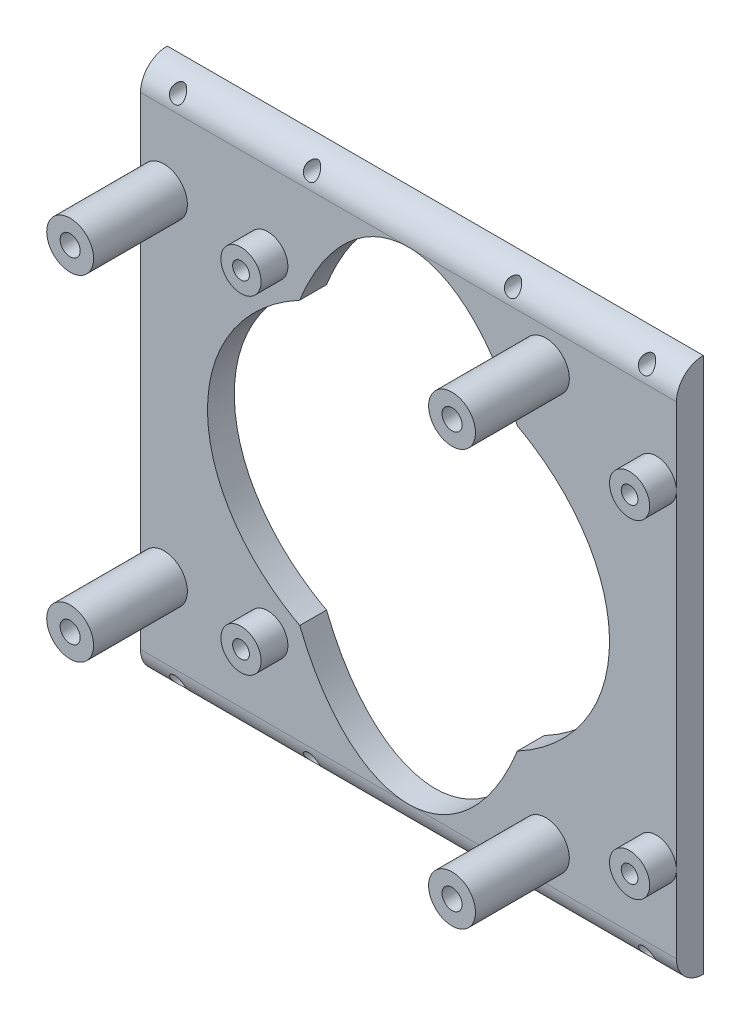
SolidWorks part; units mm, degrees
ref_plane "Alzado" through (0, 0, 0) normal (0, 0, 1) x (1, 0, 0)
ref_plane "Planta" through (0, 0, 0) normal (0, 1, 0) x (1, 0, 0)
ref_plane "Vista lateral" through (0, 0, 0) normal (1, 0, 0) x (0, 0, -1)
sketch "Croquis1" plane through (0, 0, 0) normal (0, 0, 1) x (1, 0, 0)
  line L0 (-50.9465, -21.9298) -> (-50.9465, -17.9298) construction
  line L1 (-50.9465, 58.0702) -> (29.0535, 58.0702)
  line L2 (-50.9465, 58.0702) -> (-50.9465, -21.9298)
  line L3 (-50.9465, -21.9298) -> (29.0535, -21.9298)
  line L4 (29.0535, 58.0702) -> (29.0535, -21.9298)
  line L5 (-50.9465, 58.0702) -> (-50.9465, 54.0702) construction
  line L6 (29.0535, -21.9298) -> (19.0535, -21.9298) construction
  line L7 (-50.9465, -17.9298) -> (29.0535, -17.9298)
  line L8 (-50.9465, -17.9298) -> (-50.9465, -21.9298)
  line L9 (-50.9465, -21.9298) -> (29.0535, -21.9298)
  line L10 (29.0535, -17.9298) -> (29.0535, -21.9298)
  line L11 (-50.9465, 54.0702) -> (29.0535, 54.0702)
  line L12 (-50.9465, 54.0702) -> (-50.9465, 58.0702)
  line L13 (-50.9465, 58.0702) -> (29.0535, 58.0702)
  line L14 (29.0535, 54.0702) -> (29.0535, 58.0702)
  line L15 (-50.9465, -21.9298) -> (-40.9465, -21.9298) construction
  line L16 (-50.9465, 18.0702) -> (29.0535, 18.0702) construction
  line L17 (29.0535, -21.9298) -> (19.0535, -21.9298)
  line L18 (29.0535, -21.9298) -> (29.0535, 58.0702)
  line L19 (29.0535, 58.0702) -> (19.0535, 58.0702)
  line L20 (19.0535, -21.9298) -> (19.0535, 58.0702)
  line L21 (-50.9465, 58.0702) -> (-40.9465, 58.0702)
  line L22 (-50.9465, 58.0702) -> (-50.9465, -21.9298)
  line L23 (-50.9465, -21.9298) -> (-40.9465, -21.9298)
  line L24 (-40.9465, 58.0702) -> (-40.9465, -21.9298)
  line L29 (19.0535, -21.9298) -> (9.5535, -21.9298) construction
  line L30 (29.0535, 18.0702) -> (29.0535, -6.4298) construction
  line L31 (29.0535, 18.0702) -> (29.0535, 42.5702) construction
  line L32 (29.0535, 42.5702) -> (-50.9465, 42.5702) construction
  line L33 (29.0535, -6.4298) -> (-50.9465, -6.4298) construction
  line L34 (29.0535, -6.4298) -> (26.0535, -6.4298) construction
  line L35 (-50.9465, 18.0702) -> (-50.9465, 43.0702) construction
  line L36 (-50.9465, 18.0702) -> (-50.9465, -6.9298) construction
  line L37 (-50.9465, 18.0702) -> (-50.9465, 49.0702) construction
  line L38 (-50.9465, 18.0702) -> (-50.9465, -12.9298) construction
  line L39 (-50.9465, 49.0702) -> (29.0535, 49.0702) construction
  line L40 (-50.9465, -12.9298) -> (29.0535, -12.9298) construction
  line L41 (9.5535, -21.9298) -> (9.5535, 58.0702) construction
  line L42 (9.5535, -12.9298) -> (-47.4465, -12.9298) construction
  line L43 (-47.4465, -21.9298) -> (-47.4465, 58.0702) construction
  line L44 (26.0535, -21.9298) -> (26.0535, 58.0702) construction
  line L45 (-50.9465, 43.0702) -> (29.0535, 43.0702) construction
  line L46 (-50.9465, -6.9298) -> (29.0535, -6.9298) construction
  line L47 (26.0535, -6.4298) -> (-31.9465, -6.4298) construction
  line L48 (-40.9465, 58.0702) -> (-40.9465, 68.0702) construction
  line L49 (-40.9465, -21.9298) -> (-40.9465, -31.9298) construction
  line L50 (-50.9465, -21.9298) -> (-40.9465, -31.9298) construction
  line L51 (-50.9465, -21.9298) -> (-40.9465, -21.9298)
  line L52 (-50.9465, -21.9298) -> (-50.9465, -31.9298)
  line L53 (-50.9465, -31.9298) -> (-40.9465, -31.9298)
  line L54 (-40.9465, -21.9298) -> (-40.9465, -31.9298)
  line L55 (19.0535, -21.9298) -> (29.0535, -21.9298)
  line L56 (19.0535, -21.9298) -> (19.0535, -31.9298)
  line L57 (19.0535, -31.9298) -> (29.0535, -31.9298)
  line L58 (29.0535, -21.9298) -> (29.0535, -31.9298)
  line L59 (-50.9465, 58.0702) -> (-40.9465, 58.0702)
  line L60 (-50.9465, 58.0702) -> (-50.9465, 68.0702)
  line L61 (-50.9465, 68.0702) -> (-40.9465, 68.0702)
  line L62 (-40.9465, 58.0702) -> (-40.9465, 68.0702)
  line L63 (19.0535, 58.0702) -> (29.0535, 58.0702)
  line L64 (19.0535, 58.0702) -> (19.0535, 68.0702)
  line L65 (19.0535, 68.0702) -> (29.0535, 68.0702)
  line L66 (29.0535, 58.0702) -> (29.0535, 68.0702)
  line L67 (-50.9465, -31.9298) -> (-40.9465, -21.9298) construction
  line L68 (19.0535, -21.9298) -> (29.0535, -31.9298) construction
  line L69 (19.0535, -31.9298) -> (29.0535, -21.9298) construction
  line L70 (19.0535, 68.0702) -> (29.0535, 58.0702) construction
  line L71 (29.0535, 68.0702) -> (19.0535, 58.0702) construction
  line L72 (-50.9465, 58.0702) -> (-40.9465, 68.0702) construction
  line L73 (-40.9465, 58.0702) -> (-50.9465, 68.0702) construction
  line L74 (-10.9465, 58.0702) -> (-10.9465, -21.9298)
  line L75 (-30.9465, 58.0702) -> (-30.9465, -21.9298)
  line L76 (9.0535, 58.0702) -> (9.0535, -21.9298)
  line L77 (-20.9465, 58.0702) -> (-20.9465, -21.9298)
  line L78 (-0.9465, 58.0702) -> (-0.9465, -21.9298)
  line L79 (-50.9465, 13.0702) -> (29.0535, 13.0702)
  line L80 (-50.9465, 23.0702) -> (29.0535, 23.0702)
  line L82 (-50.9465, 13.0702) -> (29.0535, 13.0702)
  line L83 (-50.9465, 13.0702) -> (-50.9465, 23.0702)
  line L84 (-50.9465, 23.0702) -> (29.0535, 23.0702)
  line L85 (29.0535, 13.0702) -> (29.0535, 23.0702)
  line L86 (-50.9465, -21.9298) -> (29.0535, -21.9298)
  line L87 (-50.9465, -21.9298) -> (-50.9465, -17.9298)
  line L88 (-50.9465, -17.9298) -> (29.0535, -17.9298)
  line L89 (29.0535, -21.9298) -> (29.0535, -17.9298)
  line L90 (-50.9465, 54.0702) -> (29.0535, 54.0702)
  line L91 (-50.9465, 54.0702) -> (-50.9465, 58.0702)
  line L92 (-50.9465, 58.0702) -> (29.0535, 58.0702)
  line L93 (29.0535, 54.0702) -> (29.0535, 58.0702)
  circle A0 centre (9.5535, -12.9298) radius 3.5
  circle A1 centre (9.5535, 49.0702) radius 3.5
  circle A2 centre (9.5535, 49.0702) radius 1.5
  circle A3 centre (9.5535, -12.9298) radius 1.5
  circle A4 centre (9.5535, 49.0702) radius 2.2
  circle A5 centre (9.5535, -12.9298) radius 2.2
  circle A12 centre (26.0535, 42.5702) radius 3
  circle A13 centre (26.0535, -6.4298) radius 3
  circle A14 centre (-47.4465, 43.0702) radius 3.5
  circle A15 centre (-47.4465, 43.0702) radius 2.2
  circle A16 centre (-47.4465, 43.0702) radius 1.5
  circle A17 centre (-47.4465, -6.9298) radius 3.5
  circle A18 centre (-47.4465, -6.9298) radius 2.2
  circle A19 centre (-47.4465, -6.9298) radius 1.5
  circle A20 centre (26.0535, -6.4298) radius 1.25
  circle A21 centre (26.0535, 42.5702) radius 1.25
  circle A22 centre (-31.9465, -6.4298) radius 3
  circle A23 centre (-31.9465, -6.4298) radius 1.25
  circle A24 centre (-31.9465, 42.5702) radius 3
  circle A25 centre (-31.9465, 42.5702) radius 1.25
  circle A26 centre (-45.9465, 63.0702) radius 1.5
  circle A27 centre (24.0535, 63.0702) radius 1.5
  circle A28 centre (24.0535, -26.9298) radius 1.5
  circle A29 centre (-45.9465, -26.9298) radius 1.5
  dimension "D15" = 57
  dimension "D16" = 58
  dimension "D19" = 20
  dimension "D1" = 80
  dimension "D2" = 80
  dimension "D3" = 4
  dimension "D4" = 4
  dimension "D5" = 10
  dimension "D6" = 10
  dimension "D7" = 9.5
  dimension "D8" = 24.5
  dimension "D9" = 24.5
  dimension "D10" = 3
  dimension "D11" = 25
  dimension "D12" = 25
  dimension "D13" = 31
  dimension "D14" = 31
  dimension "D20" = 20
  dimension "D21" = 10
  dimension "D22" = 10
  dimension "D23" = 5
  dimension "D24" = 5
extrude "Saliente-Extruir5" add sketch "Croquis1" along normal blind 4 contours L1 L62 L61 L60 A26 | L13 L66 L65 L64 A27 | L58 L9 L56 L57 A28 | L54 L3 L52 L53 A29 | L24 L7 L2 L3 | L75 L7 L24 L9 | L77 L7 L75 L3 | L7 L77 L9 L74 | L78 L7 L74 L3 | L7 L78 L9 L76 | L7 L76 L9 L20 | L20 L9 L4 L7 | A13 A20 | A20 | L4 A13 L18 L79 L20 L7 | L22 A17 L2 L7 L24 L79 | A17 A18 | A18 A19 | A19 | L80 L22 L79 L24 | L80 L24 L79 L75 | L80 L75 L79 L77 | L80 L77 L79 L74 | L80 L74 L79 L78 | L80 L78 L79 L76 | L80 L76 L79 L20 | L80 L20 L79 L18 | L2 A14 L22 L80 L24 L11 | L24 L1 L2 L11 | A14 A15 | A15 A16 | A16 | L75 L13 L24 L11 | L77 L1 L75 L11 | L13 L77 L11 L74 | L78 L1 L74 L11 | L13 L78 L11 L76 | L13 L76 L11 L20 | L20 L11 L4 L13 | L18 A12 L4 L11 L20 L80 | A12 A21 | A21 region at (-50.8051, 63.0702, 0) region at (-45.9465, 56.0702, 0) region at (-35.9465, 56.0702, 0) region at (-47.4465, 46.4712, 0) region at (-45.7339, 37.9323, 0) region at (-25.9465, 56.0702, 0) region at (-15.9465, 56.0702, 0) region at (-35.9465, 18.0702, 0) region at (-45.9465, 18.0702, 0) region at (-5.9465, 56.0702, 0) region at (-47.4465, -3.5288, 0) region at (-45.7339, -1.792, 0) region at (-25.9465, 18.0702, 0) region at (4.0535, 56.0702, 0) region at (-15.9465, 18.0702, 0) region at (-45.9465, -19.9298, 0) region at (-35.9465, -19.9298, 0) region at (14.0535, 56.0702, 0) region at (-5.9465, 18.0702, 0) region at (-25.9465, -19.9298, 0) region at (-41.0879, -26.9298, 0) region at (19.1949, 63.0702, 0) region at (24.0535, 56.0702, 0) region at (4.0535, 18.0702, 0) region at (-15.9465, -19.9298, 0) region at (23.1383, 42.5702, 0) region at (23.8528, 38.1687, 0) region at (14.0535, 18.0702, 0) region at (-5.9465, -19.9298, 0) region at (24.0535, 18.0702, 0) region at (4.0535, -19.9298, 0) region at (23.1383, -6.4298, 0) region at (23.8528, -2.0284, 0) region at (14.0535, -19.9298, 0) region at (24.0535, -19.9298, 0) region at (24.0535, -22.0712, 0) region at (-49.5843, 43.0702, 0) region at (-47.4465, 43.0702, 0) region at (-49.5843, -6.9298, 0) region at (-47.4465, -6.9298, 0) region at (26.0535, -6.4298, 0) region at (26.0535, 42.5702, 0)
extrude "Saliente-Extruir6" add sketch "Croquis1<6>" along normal blind 20.4 from surface contours L24 L1 L2 L11 | L77 L1 L75 L11 | L20 L11 L4 L13 | L13 L78 L11 L76 | L24 L7 L2 L3 | L77 L7 L75 L3 | L7 L78 L9 L76 | L20 L9 L4 L7 region at (-45.9465, 56.0702, 0) region at (-25.9465, 56.0702, 0) region at (4.0535, 56.0702, 0) region at (-45.9465, -19.9298, 0) region at (-25.9465, -19.9298, 0) region at (24.0535, 56.0702, 0) region at (4.0535, -19.9298, 0) region at (24.0535, -19.9298, 0) starting at face at (-10.9465, -2.4298, 4)
sketch "Croquis1<6>" plane through (0, 0, 0) normal (0, 0, 1) x (1, 0, 0) same geometry as "Croquis1"
extrude "Saliente-Extruir7" add sketch "Croquis1<7>" along normal blind 4 from surface contours L24 L1 L2 L11 | L75 L13 L24 L11 | L13 L77 L11 L74 | L78 L1 L74 L11 | L13 L78 L11 L76 | L77 L1 L75 L11 | L13 L76 L11 L20 | L18 A12 L4 L11 L20 L80 | L2 A14 L22 L80 L24 L11 | A24 L75 L11 L24 L80 | A14 A15 | A15 A16 | A16 | A12 A21 | A21 | L20 L11 L4 L13 | A25 L75 A24 | L75 A25 | A25 L75 A24 | L75 A25 | A24 L75 L80 L77 L11 | L77 L80 L74 L11 | L74 L80 L78 L11 | A1 L76 L11 L78 L80 | A4 L76 A1 | L76 A4 A2 | L76 A2 | L76 A2 | L76 A4 A2 | A4 L76 A1 | A1 L76 L80 L20 L11 | L80 L20 L79 L18 | L80 L76 L79 L20 | L80 L78 L79 L76 | L80 L74 L79 L78 | L80 L77 L79 L74 | L80 L75 L79 L77 | L80 L24 L79 L75 | L80 L22 L79 L24 | A22 L75 L79 L24 L7 | A22 L75 L7 L77 L79 | L79 L77 L7 L74 | L79 L74 L7 L78 | A0 L76 L79 L78 L7 | A0 L76 L7 L20 L79 | L22 A17 L2 L7 L24 L79 | A17 A18 | A18 A19 | A19 | A23 L75 A22 | L75 A23 | L75 A23 | A23 L75 A22 | A13 A20 | A20 | L76 A3 | L76 A3 | L76 A5 A3 | A5 L76 A0 | L76 A5 A3 | A5 L76 A0 | L20 L9 L4 L7 | L7 L76 L9 L20 | L7 L78 L9 L76 | L78 L7 L74 L3 | L7 L77 L9 L74 | L77 L7 L75 L3 | L75 L7 L24 L9 | L24 L7 L2 L3 | L4 A13 L18 L79 L20 L7 region at (-45.9465, 56.0702, 0) region at (-35.9465, 56.0702, 0) region at (-47.4465, 46.4712, 0) region at (-45.7339, 37.9323, 0) region at (-25.9465, 56.0702, 0) region at (-36.1707, 38.294, 0) region at (-15.9465, 56.0702, 0) region at (-25.8325, 38.4608, 0) region at (-35.9465, 18.0702, 0) region at (-45.9465, 18.0702, 0) region at (-5.9465, 56.0702, 0) region at (-15.9465, 38.5702, 0) region at (-30.0948, 42.5702, 0) region at (-31.0186, 44.3594, 0) region at (-36.1707, -2.1536, 0) region at (-47.4465, -3.5288, 0) region at (-45.7339, -1.792, 0) region at (-25.9465, 18.0702, 0) region at (4.0535, 56.0702, 0) region at (-5.9465, 38.5702, 0) region at (-15.9465, 18.0702, 0) region at (-30.8456, 42.5702, 0) region at (-32.007, 42.5702, 0) region at (-45.9465, -19.9298, 0) region at (-35.9465, -19.9298, 0) region at (-25.8325, -2.3205, 0) region at (14.0535, 56.0702, 0) region at (3.8532, 38.008, 0) region at (-5.9465, 18.0702, 0) region at (-15.9465, -2.4298, 0) region at (-25.9465, -19.9298, 0) region at (-30.0948, -6.4298, 0) region at (-31.0186, -4.6406, 0) region at (24.0535, 56.0702, 0) region at (14.3131, 37.7394, 0) region at (4.0535, 18.0702, 0) region at (-5.9465, -2.4298, 0) region at (-15.9465, -19.9298, 0) region at (-30.8456, -6.4298, 0) region at (-32.007, -6.4298, 0) region at (23.1383, 42.5702, 0) region at (23.8528, 38.1687, 0) region at (11.792, 51.655, 0) region at (8.978, 51.8734, 0) region at (3.8532, -1.8676, 0) region at (14.0535, 18.0702, 0) region at (-5.9465, -19.9298, 0) region at (24.0535, 18.0702, 0) region at (10.8889, 50.7531, 0) region at (9.0074, 50.8485, 0) region at (4.0535, -19.9298, 0) region at (14.3131, -1.599, 0) region at (23.1383, -6.4298, 0) region at (23.8528, -2.0284, 0) region at (9.9301, 49.0702, 0) region at (8.6393, 49.0702, 0) region at (14.0535, -19.9298, 0) region at (11.792, -10.345, 0) region at (8.978, -10.1266, 0) region at (24.0535, -19.9298, 0)
sketch "Croquis1<7>" plane through (0, 0, 0) normal (0, 0, 1) x (1, 0, 0) same geometry as "Croquis1"
extrude "Saliente-Extruir9" add sketch "Croquis1<10>" along normal blind 4 from surface contours A24 | A12 | A13 | A22 starting at face at (-10.9465, 18.0702, 28.4)
sketch "Croquis1<10>" plane through (0, 0, 0) normal (0, 0, 1) x (1, 0, 0) same geometry as "Croquis1"
extrude "Saliente-Extruir10" add sketch "Croquis1<11>" along normal blind 14 from surface contours A14 | A17 | A0 | A1 starting at face at (-34.9465, -6.4298, 28.4)
sketch "Croquis1<11>" plane through (0, 0, 0) normal (0, 0, 1) x (1, 0, 0) same geometry as "Croquis1"
extrude "Cortar-Extruir1" cut sketch "Croquis1<12>" against normal blind 14 and the other way blind 14 from surface contours A19 | A23 | A3 | A20 | A21 | A2 | A25 | A16 starting at face at (6.0535, 49.0702, 28.4)
sketch "Croquis1<12>" plane through (0, 0, 0) normal (0, 0, 1) x (1, 0, 0) same geometry as "Croquis1"
extrude "Cortar-Extruir2" cut sketch "Croquis1<13>" along normal blind 15 from surface contours A5 | A18 | A15 | A4 starting at face at (-33.1965, -6.4298, 24.4)
sketch "Croquis1<13>" plane through (0, 0, 0) normal (0, 0, 1) x (1, 0, 0) same geometry as "Croquis1"
fillet "Redondeo2" 2 edges at (-40.9465, 68.0702, 2) (-50.9465, 68.0702, 2) type full round first side face at (-40.9465, 63.0702, 2) second side face at (-50.9465, 18.0702, 12.96) middle face at (-45.9465, 68.0702, 2)
fillet "Redondeo3" 2 edges at (-50.9465, -31.9298, 2) (-40.9465, -31.9298, 2) type full round first side face at (-50.9465, 17.0702, 12.96) second side face at (-40.9465, -26.9298, 2) middle face at (-45.9465, -31.9298, 2)
fillet "Redondeo4" 2 edges at (19.0535, -31.9298, 2) (29.0535, -31.9298, 2) type full round first side face at (19.0535, -26.9298, 2) second side face at (29.0535, 18.0702, 12.96) middle face at (24.0535, -31.9298, 2)
fillet "Redondeo5" 2 edges at (19.0535, 68.0702, 2) (29.0535, 68.0702, 2) type full round first side face at (19.0535, 63.0702, 2) second side face at (29.0535, 19.0702, 12.96) middle face at (24.0535, 68.0702, 2)
sketch "Croquis2" plane through (0, 0, 0) normal (0, 0, 1) x (1, 0, 0)
  line L0 (-50.9465, -21.9298) -> (-50.9465, -17.9298) construction
  line L1 (-50.9465, 58.0702) -> (29.0535, 58.0702)
  line L2 (-50.9465, 58.0702) -> (-50.9465, -21.9298)
  line L3 (-50.9465, -21.9298) -> (29.0535, -21.9298)
  line L4 (29.0535, 58.0702) -> (29.0535, -21.9298)
  line L5 (-50.9465, 58.0702) -> (-50.9465, 54.0702) construction
  line L6 (29.0535, -21.9298) -> (19.0535, -21.9298) construction
  line L7 (-50.9465, -17.9298) -> (29.0535, -17.9298)
  line L8 (-50.9465, -17.9298) -> (-50.9465, -21.9298)
  line L9 (-50.9465, -21.9298) -> (29.0535, -21.9298)
  line L10 (29.0535, -17.9298) -> (29.0535, -21.9298)
  line L11 (-50.9465, 54.0702) -> (29.0535, 54.0702)
  line L12 (-50.9465, 54.0702) -> (-50.9465, 58.0702)
  line L13 (-50.9465, 58.0702) -> (29.0535, 58.0702)
  line L14 (29.0535, 54.0702) -> (29.0535, 58.0702)
  line L15 (-50.9465, -21.9298) -> (-40.9465, -21.9298) construction
  line L16 (-50.9465, 18.0702) -> (29.0535, 18.0702) construction
  line L17 (29.0535, -21.9298) -> (19.0535, -21.9298)
  line L18 (29.0535, -21.9298) -> (29.0535, 58.0702)
  line L19 (29.0535, 58.0702) -> (19.0535, 58.0702)
  line L20 (19.0535, -21.9298) -> (19.0535, 58.0702)
  line L21 (-50.9465, 58.0702) -> (-40.9465, 58.0702)
  line L22 (-50.9465, 58.0702) -> (-50.9465, -21.9298)
  line L23 (-50.9465, -21.9298) -> (-40.9465, -21.9298)
  line L24 (-40.9465, 58.0702) -> (-40.9465, -21.9298)
  line L29 (19.0535, -21.9298) -> (9.5535, -21.9298) construction
  line L30 (29.0535, 18.0702) -> (29.0535, -6.4298) construction
  line L31 (29.0535, 18.0702) -> (29.0535, 42.5702) construction
  line L32 (29.0535, 42.5702) -> (-50.9465, 42.5702) construction
  line L33 (29.0535, -6.4298) -> (-50.9465, -6.4298) construction
  line L34 (29.0535, -6.4298) -> (26.0535, -6.4298) construction
  line L35 (-50.9465, 18.0702) -> (-50.9465, 43.0702) construction
  line L36 (-50.9465, 18.0702) -> (-50.9465, -6.9298) construction
  line L37 (-50.9465, 18.0702) -> (-50.9465, 49.0702) construction
  line L38 (-50.9465, 18.0702) -> (-50.9465, -12.9298) construction
  line L39 (-50.9465, 49.0702) -> (29.0535, 49.0702) construction
  line L40 (-50.9465, -12.9298) -> (29.0535, -12.9298) construction
  line L41 (9.5535, -21.9298) -> (9.5535, 58.0702) construction
  line L42 (9.5535, -12.9298) -> (-47.4465, -12.9298) construction
  line L43 (-47.4465, -21.9298) -> (-47.4465, 58.0702) construction
  line L44 (26.0535, -21.9298) -> (26.0535, 58.0702) construction
  line L45 (-50.9465, 43.0702) -> (29.0535, 43.0702) construction
  line L46 (-50.9465, -6.9298) -> (29.0535, -6.9298) construction
  line L47 (26.0535, -6.4298) -> (-31.9465, -6.4298) construction
  line L48 (-40.9465, 58.0702) -> (-40.9465, 68.0702) construction
  line L49 (-40.9465, -21.9298) -> (-40.9465, -31.9298) construction
  line L50 (-50.9465, -21.9298) -> (-40.9465, -31.9298) construction
  line L51 (-50.9465, -21.9298) -> (-40.9465, -21.9298)
  line L52 (-50.9465, -21.9298) -> (-50.9465, -31.9298)
  line L53 (-50.9465, -31.9298) -> (-40.9465, -31.9298)
  line L54 (-40.9465, -21.9298) -> (-40.9465, -31.9298)
  line L55 (19.0535, -21.9298) -> (29.0535, -21.9298)
  line L56 (19.0535, -21.9298) -> (19.0535, -31.9298)
  line L57 (19.0535, -31.9298) -> (29.0535, -31.9298)
  line L58 (29.0535, -21.9298) -> (29.0535, -31.9298)
  line L59 (-50.9465, 58.0702) -> (-40.9465, 58.0702)
  line L60 (-50.9465, 58.0702) -> (-50.9465, 68.0702)
  line L61 (-50.9465, 68.0702) -> (-40.9465, 68.0702)
  line L62 (-40.9465, 58.0702) -> (-40.9465, 68.0702)
  line L63 (19.0535, 58.0702) -> (29.0535, 58.0702)
  line L64 (19.0535, 58.0702) -> (19.0535, 68.0702)
  line L65 (19.0535, 68.0702) -> (29.0535, 68.0702)
  line L66 (29.0535, 58.0702) -> (29.0535, 68.0702)
  line L67 (-50.9465, -31.9298) -> (-40.9465, -21.9298) construction
  line L68 (19.0535, -21.9298) -> (29.0535, -31.9298) construction
  line L69 (19.0535, -31.9298) -> (29.0535, -21.9298) construction
  line L70 (19.0535, 68.0702) -> (29.0535, 58.0702) construction
  line L71 (29.0535, 68.0702) -> (19.0535, 58.0702) construction
  line L72 (-50.9465, 58.0702) -> (-40.9465, 68.0702) construction
  line L73 (-40.9465, 58.0702) -> (-50.9465, 68.0702) construction
  line L74 (-10.9465, 58.0702) -> (-10.9465, -21.9298)
  line L75 (-30.9465, 58.0702) -> (-30.9465, -21.9298)
  line L76 (9.0535, 58.0702) -> (9.0535, -21.9298)
  line L77 (-20.9465, 58.0702) -> (-20.9465, -21.9298)
  line L78 (-0.9465, 58.0702) -> (-0.9465, -21.9298)
  line L79 (-50.9465, 13.0702) -> (29.0535, 13.0702)
  line L80 (-50.9465, 23.0702) -> (29.0535, 23.0702)
  line L82 (-50.9465, 13.0702) -> (29.0535, 13.0702)
  line L83 (-50.9465, 13.0702) -> (-50.9465, 23.0702)
  line L84 (-50.9465, 23.0702) -> (29.0535, 23.0702)
  line L85 (29.0535, 13.0702) -> (29.0535, 23.0702)
  line L86 (-50.9465, -21.9298) -> (29.0535, -21.9298)
  line L87 (-50.9465, -21.9298) -> (-50.9465, -17.9298)
  line L88 (-50.9465, -17.9298) -> (29.0535, -17.9298)
  line L89 (29.0535, -21.9298) -> (29.0535, -17.9298)
  line L90 (-50.9465, 54.0702) -> (29.0535, 54.0702)
  line L91 (-50.9465, 54.0702) -> (-50.9465, 58.0702)
  line L92 (-50.9465, 58.0702) -> (29.0535, 58.0702)
  line L93 (29.0535, 54.0702) -> (29.0535, 58.0702)
  circle A0 centre (9.5535, -12.9298) radius 3.5
  circle A1 centre (9.5535, 49.0702) radius 3.5
  circle A2 centre (9.5535, 49.0702) radius 1.5
  circle A3 centre (9.5535, -12.9298) radius 1.5
  circle A4 centre (9.5535, 49.0702) radius 2.2
  circle A5 centre (9.5535, -12.9298) radius 2.2
  circle A12 centre (26.0535, 42.5702) radius 3
  circle A13 centre (26.0535, -6.4298) radius 3
  circle A14 centre (-47.4465, 43.0702) radius 3.5
  circle A15 centre (-47.4465, 43.0702) radius 2.2
  circle A16 centre (-47.4465, 43.0702) radius 1.5
  circle A17 centre (-47.4465, -6.9298) radius 3.5
  circle A18 centre (-47.4465, -6.9298) radius 2.2
  circle A19 centre (-47.4465, -6.9298) radius 1.5
  circle A20 centre (26.0535, -6.4298) radius 1.25
  circle A21 centre (26.0535, 42.5702) radius 1.25
  circle A22 centre (-31.9465, -6.4298) radius 3
  circle A23 centre (-31.9465, -6.4298) radius 1.25
  circle A24 centre (-31.9465, 42.5702) radius 3
  circle A25 centre (-31.9465, 42.5702) radius 1.25
  circle A26 centre (-45.9465, 63.0702) radius 1.5
  circle A27 centre (24.0535, 63.0702) radius 1.5
  circle A28 centre (24.0535, -26.9298) radius 1.5
  circle A29 centre (-45.9465, -26.9298) radius 1.5
  ellipse E0 centre (-10.9465, 18.0702) end of major axis (-40.9465, 18.0702) minor radius 25
  ellipse E1 centre (-10.9465, 18.0702) end of major axis (-10.9465, -17.9298) minor radius 20
  dimension "D15" = 57
  dimension "D16" = 58
  dimension "D19" = 20
  dimension "D1" = 80
  dimension "D2" = 80
  dimension "D3" = 4
  dimension "D4" = 4
  dimension "D5" = 10
  dimension "D6" = 10
  dimension "D7" = 9.5
  dimension "D8" = 24.5
  dimension "D9" = 24.5
  dimension "D10" = 3
  dimension "D11" = 25
  dimension "D12" = 25
  dimension "D13" = 31
  dimension "D14" = 31
  dimension "D20" = 20
  dimension "D21" = 10
  dimension "D22" = 10
  dimension "D23" = 5
  dimension "D24" = 5
fillet "Redondeo6" radius 4 1 edges at (-10.9465, -21.9298, 28.4) type face fillet first side face at (-10.9465, -21.9298, 11.65) second side face at (6.0535, 49.0702, 28.4)
fillet "Redondeo7" radius 4 1 edges at (-10.9465, 58.0702, 28.4) type face fillet first side face at (-10.9465, 58.0702, 11.65) second side face at (6.0535, 49.0702, 28.4)
extrude "Cortar-Extruir6" cut sketch "Croquis2" against normal blind 8 from surface contours E1 | E0 starting at face at (6.0535, 49.0702, 28.4)
sketch "Croquis3" plane through (0, -21.9298, 0) normal (0, -1, 0) x (1, 0, 0)
  line L0 (-40.9465, 24.4) -> (-50.9465, 24.4) construction
  line L1 (-50.9465, 24.4) -> (29.0535, 24.4)
  line L2 (-50.9465, 24.4) -> (-50.9465, 0)
  line L3 (-50.9465, 0) -> (29.0535, 0)
  line L4 (29.0535, 24.4) -> (29.0535, 0)
extrude "Cortar-Extruir7" cut sketch "Croquis3" against normal blind 90 and the other way blind 10
sketch "Croquis4" plane through (0, 0, 24.4) normal (0, 0, -1) x (-1, 0, 0)
  line L0 (50.9465, 58.0702) -> (50.9465, 54.0702) construction
  line L1 (50.9465, 54.0702) -> (-29.0535, 54.0702) construction
  line L2 (-29.0535, -21.9298) -> (-29.0535, 58.0702) construction
  line L3 (-29.0535, 54.0702) -> (-29.0535, 58.0702) construction
  line L4 (-29.0535, 58.0702) -> (50.9465, 58.0702) construction
  line L5 (-29.0535, 58.0702) -> (-19.0535, 58.0702) construction
  line L6 (50.9465, 58.0702) -> (-29.0535, 58.0702)
  line L7 (50.9465, 58.0702) -> (50.9465, 54.0702)
  line L8 (50.9465, 54.0702) -> (-29.0535, 54.0702)
  line L9 (-29.0535, 58.0702) -> (-29.0535, 54.0702)
  line L10 (-19.0535, 58.0702) -> (-9.0535, 58.0702) construction
  line L11 (-9.0535, 58.0702) -> (0.9465, 58.0702) construction
  line L12 (50.9465, 58.0702) -> (40.9465, 58.0702) construction
  line L13 (40.9465, 58.0702) -> (30.9465, 58.0702) construction
  line L14 (30.9465, 58.0702) -> (20.9465, 58.0702) construction
  line L15 (-19.0535, 58.0702) -> (-19.0535, -21.9298) construction
  line L16 (50.9465, -21.9298) -> (-29.0535, -21.9298)
  line L17 (50.9465, -21.9298) -> (50.9465, -17.9298)
  line L18 (50.9465, -17.9298) -> (-29.0535, -17.9298)
  line L19 (-29.0535, -21.9298) -> (-29.0535, -17.9298)
  line L20 (-19.0535, -21.9298) -> (-9.0535, -21.9298) construction
  line L21 (-9.0535, -21.9298) -> (-9.0535, 58.0702) construction
  line L22 (-9.0535, 58.0702) -> (0.9465, 58.0702) construction
  line L23 (0.9465, 58.0702) -> (0.9465, -21.9298) construction
  line L24 (0.9465, -21.9298) -> (20.9465, 58.0702) construction
  line L25 (20.9465, 58.0702) -> (20.9465, -21.9298) construction
  line L26 (20.9465, -21.9298) -> (30.9465, -21.9298) construction
  line L27 (30.9465, -21.9298) -> (30.9465, 58.0702) construction
  line L28 (30.9465, 58.0702) -> (40.9465, 58.0702) construction
  line L29 (40.9465, 58.0702) -> (40.9465, -21.9298) construction
  line L30 (50.9465, 56.0702) -> (-29.0535, 56.0702)
  line L31 (50.9465, 58.0702) -> (40.9465, 58.0702)
  line L32 (50.9465, 58.0702) -> (50.9465, 54.0702)
  line L33 (50.9465, 54.0702) -> (40.9465, 54.0702)
  line L34 (40.9465, 58.0702) -> (40.9465, 54.0702)
  line L35 (30.9465, 58.0702) -> (20.9465, 58.0702)
  line L36 (30.9465, 58.0702) -> (30.9465, 54.0702)
  line L37 (30.9465, 54.0702) -> (20.9465, 54.0702)
  line L38 (20.9465, 58.0702) -> (20.9465, 54.0702)
  line L39 (0.9465, 58.0702) -> (-9.0535, 58.0702)
  line L40 (0.9465, 58.0702) -> (0.9465, 54.0702)
  line L41 (0.9465, 54.0702) -> (-9.0535, 54.0702)
  line L42 (-9.0535, 58.0702) -> (-9.0535, 54.0702)
  line L43 (-19.0535, 58.0702) -> (-29.0535, 58.0702)
  line L44 (-19.0535, 58.0702) -> (-19.0535, 54.0702)
  line L45 (-19.0535, 54.0702) -> (-29.0535, 54.0702)
  line L46 (-29.0535, 58.0702) -> (-29.0535, 54.0702)
  line L47 (-29.0535, -21.9298) -> (-19.0535, -21.9298)
  line L48 (-29.0535, -21.9298) -> (-29.0535, -17.9298)
  line L49 (-29.0535, -17.9298) -> (-19.0535, -17.9298)
  line L50 (-19.0535, -21.9298) -> (-19.0535, -17.9298)
  line L51 (-9.0535, -21.9298) -> (0.9465, -21.9298)
  line L52 (-9.0535, -21.9298) -> (-9.0535, -17.9298)
  line L53 (-9.0535, -17.9298) -> (0.9465, -17.9298)
  line L54 (0.9465, -21.9298) -> (0.9465, -17.9298)
  line L55 (20.9465, -21.9298) -> (30.9465, -21.9298)
  line L56 (20.9465, -21.9298) -> (20.9465, -17.9298)
  line L57 (20.9465, -17.9298) -> (30.9465, -17.9298)
  line L58 (30.9465, -21.9298) -> (30.9465, -17.9298)
  line L59 (40.9465, -21.9298) -> (50.9465, -21.9298)
  line L60 (40.9465, -21.9298) -> (40.9465, -17.9298)
  line L61 (40.9465, -17.9298) -> (50.9465, -17.9298)
  line L62 (50.9465, -21.9298) -> (50.9465, -17.9298)
  line L63 (-29.0535, 54.0702) -> (-19.0535, 58.0702) construction
  line L64 (-9.0535, 54.0702) -> (0.9465, 58.0702) construction
  line L65 (30.9465, 58.0702) -> (20.9465, 54.0702) construction
  line L66 (50.9465, 58.0702) -> (40.9465, 54.0702) construction
  line L67 (50.9465, -17.9298) -> (40.9465, -21.9298) construction
  line L68 (30.9465, -17.9298) -> (20.9465, -21.9298) construction
  line L69 (0.9465, -17.9298) -> (-9.0535, -21.9298) construction
  line L70 (-19.0535, -17.9298) -> (-29.0535, -21.9298) construction
  line L71 (-29.0535, -19.9298) -> (50.9465, -19.9298) construction
  circle A0 centre (45.9465, 56.0702) radius 1.1
  circle A1 centre (25.9465, 56.0702) radius 1.1
  circle A2 centre (-4.0535, 56.0702) radius 1.1
  circle A3 centre (-24.0535, 56.0702) radius 1.1
  circle A4 centre (-24.0535, -19.9298) radius 1.1
  circle A5 centre (-4.0535, -19.9298) radius 1.1
  circle A6 centre (25.9465, -19.9298) radius 1.1
  circle A7 centre (45.9465, -19.9298) radius 1.1
  dimension "D1" = 10
  dimension "D2" = 10
  dimension "D3" = 10
  dimension "D4" = 10
  dimension "D5" = 10
  dimension "D6" = 10
extrude "Cortar-Extruir8" cut sketch "Croquis4" against normal blind 17 contours A0 | A1 | A2 | A3 | A4 | A5 | A6 | A7
